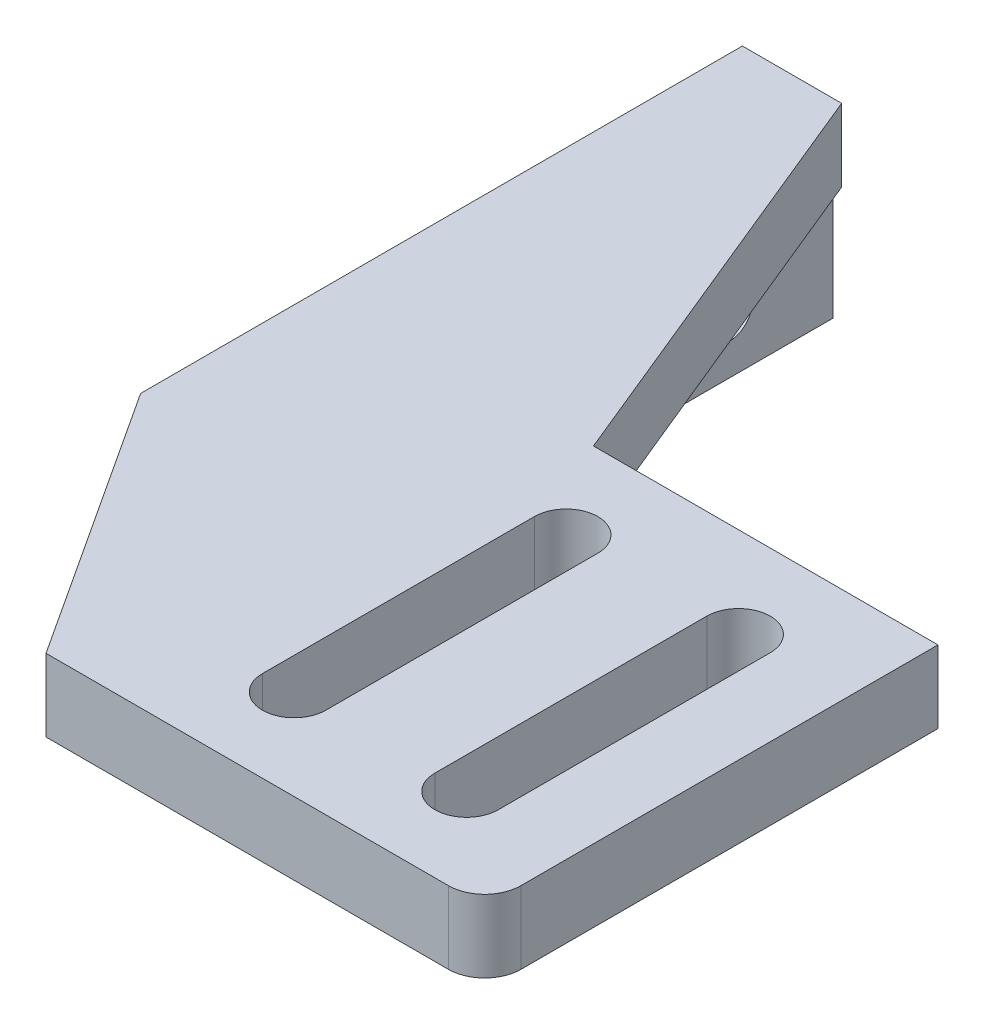
SolidWorks part; units mm, degrees
ref_plane "Piano frontale" through (0, 0, 0) normal (0, 0, 1) x (1, 0, 0)
ref_plane "Piano superiore" through (0, 0, 0) normal (0, 1, 0) x (1, 0, 0)
ref_plane "Piano destro" through (0, 0, 0) normal (1, 0, 0) x (0, 0, -1)
ref_plane "Piano1" through (0, 40, 0) normal (0, 1, 0) x (1, 0, 0)
sketch "Schizzo18" plane through (0, 40, 0) normal (0, 1, 0) x (1, 0, 0)
  line L0 (25, -16) -> (-9, -16)
  line L1 (25, -16) -> (25, 9)
  line L2 (25, 9) -> (6, 9)
  line L3 (-9, 32.2124) -> (-3.5247, 32.2124)
  line L4 (-9, -16) -> (-9, 32.2124)
  line L5 (-3.5247, 32.2124) -> (6, 9)
  line L6 (19, -16) -> (19, 9) construction
  line L7 (-9, -28.4145) -> (-9, 27.2974) construction
  line L8 (29.4558, 9) -> (-19.1855, 9) construction
  line L9 (25, -28.4145) -> (25, 27.2974) construction
  line L10 (29.4558, -16) -> (-19.1855, -16) construction
  line L11 (25, -11) -> (-9, -11) construction
  line L12 (25, 4) -> (-9, 4) construction
  line L13 (19, -11) -> (19, 4) construction
  line L14 (17.25, -11) -> (17.25, 4)
  line L15 (20.75, -11) -> (20.75, 4)
  line L16 (9.4906, -11) -> (9.4906, 4) construction
  line L17 (7.7406, -11) -> (7.7406, 4)
  line L18 (11.2406, -11) -> (11.2406, 4)
  arc A0 (17.25, -11) -> (20.75, -11) centre (19, -11) ccw
  arc A1 (20.75, 4) -> (17.25, 4) centre (19, 4) ccw
  arc A2 (7.7406, -11) -> (11.2406, -11) centre (9.4906, -11) ccw
  arc A3 (11.2406, 4) -> (7.7406, 4) centre (9.4906, 4) ccw
  point P22 (19, -3.5)
  point P29 (9.4906, -3.5)
  dimension "D6" = 15
  dimension "D1" = 6
  dimension "D2" = 25
  dimension "D3" = 34
  dimension "D4" = 5
  dimension "D5" = 15
extrude "Estrusione-Estrusione8" add sketch "Schizzo18" along normal blind 4 separate body
sketch "Schizzo19" plane through (0, 40, 0) normal (0, -1, 0) x (1, 0, 0)
  line L0 (-3.5247, -32.2124) -> (-9, -32.2124) construction
  line L1 (-9, 16) -> (-4, 16)
  line L2 (-9, 16) -> (-9, -32.2124)
  line L3 (-9, -32.2124) -> (-4, -32.2124)
  line L4 (-4, 16) -> (-4, -32.2124)
  dimension "D1" = 5
extrude "Estrusione-Estrusione9" add sketch "Schizzo19" along normal blind 6.5
sketch "Schizzo20" plane through (-9, 0, 0) normal (-1, 0, 0) x (0, 0, 1)
  line L0 (3.5, 44) -> (3.5, 33.5) construction
  line L1 (11, 44) -> (-4, 44) construction
  line L2 (16, 33.5) -> (-32.2124, 33.5) construction
  line L3 (-21.5, 44) -> (-21.5, 33.5) construction
  line L4 (-26.5, 44) -> (-26.5, 33.5) construction
  line L13 (-16.5, 44) -> (-16.5, 33.5) construction
  line L14 (-23.6103, 33.5) -> (25.3232, 33.5) construction
  line L15 (-23.6103, 36.5) -> (25.3232, 36.5) construction
  circle A0 centre (-26.5, 36.5) radius 1.25
  circle A1 centre (-16.5, 36.5) radius 1.25
  dimension "D5" = 2.5
  dimension "D1" = 25
  dimension "D2" = 5
  dimension "D3" = 5
  dimension "D4" = 3
extrude "Taglio-Estrusione9" cut sketch "Schizzo20" against normal blind 6
sketch "Schizzo21" plane through (-9, 0, 0) normal (-1, 0, 0) x (0, 0, 1)
  line L0 (16, 23.2712) -> (16, 48.2769) construction
  line L1 (1, 23.2712) -> (1, 48.2769) construction
  line L2 (16, 44) -> (16, 40.1473)
  dimension "D1" = 15
sketch "Schizzo24" plane through (0, 44, 0) normal (0, 1, 0) x (1, 0, 0)
  line L0 (-9, -16) -> (25, -16) construction
  line L2 (0.8051, -16) -> (-9, -0.979)
  line L3 (-9, 32.2124) -> (-9, -16) construction
  line L4 (-9, -0.979) -> (-9, -16)
  line L5 (-9, -16) -> (0.8051, -16)
extrude "Taglio-Estrusione13" cut sketch "Schizzo24" against normal blind 21
ref_plane "Piano2" through (0, 0, 0.979) normal (0, 0, 1) x (1, 0, 0)
sketch "Schizzo26" plane through (0, 0, 0.979) normal (0, 0, 1) x (1, 0, 0)
  line L0 (-9, 23.2712) -> (-9, 48.2769) construction
  line L1 (-4, 33.5) -> (-9, 33.5)
  line L2 (-4, 33.5) -> (-4, 40)
  line L3 (-4, 40) -> (-9, 40)
  line L4 (-9, 33.5) -> (-9, 40)
  line L5 (18.7, 40) -> (-18.7, 40) construction
extrude "Taglio-Estrusione15" cut sketch "Schizzo26" along normal blind 21
fillet "Raccordo1" radius 4 1 edges at (-6.5, 33.5, 0.979) type face fillet first side face at (-6.5, 36.75, 0.979) second side face at (-6.5, 33.5, -15.6167)
fillet "Raccordo2" radius 2 1 edges at (25, 42, 16) type face fillet first side face at (9.8782, 42, 16) second side face at (25, 42, 3.5)
